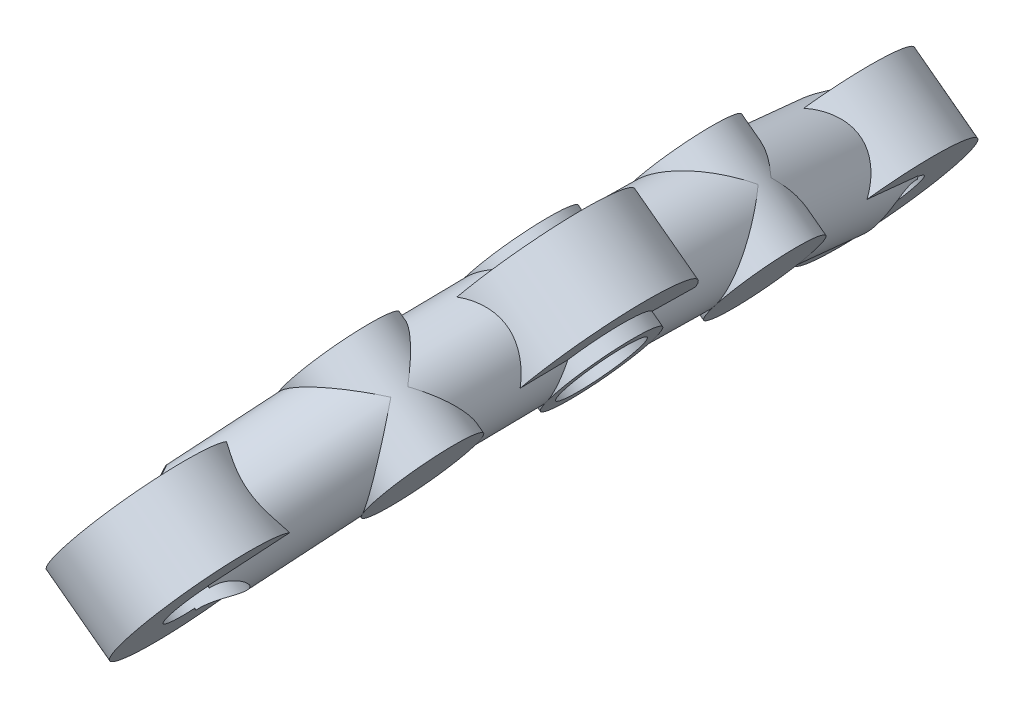
SolidWorks part; units mm, degrees
ref_plane "Alzado" through (0, 0, 0) normal (0, 0, 1) x (1, 0, 0)
ref_plane "Planta" through (0, 0, 0) normal (0, 1, 0) x (1, 0, 0)
ref_plane "Vista lateral" through (0, 0, 0) normal (1, 0, 0) x (0, 0, -1)
sketch3d "Sk_Arco_1"
  line L0 (-231.3637, 348.9396, -26) -> (-228.3681, 352.9429, -13)
  dimension "D1" = 13.9284
sweep "Arco_1" add path "Sk_Arco_1" circular profile diameter 8 parameters "D3"=8
sketch3d "Sk_Arco_2"
  line L0 (-228.3681, 352.9429, -13) -> (-227.769, 353.7435, 0)
  dimension "D1" = 13.0384
sweep "Arco_2" add path "Sk_Arco_2" circular profile diameter 8 parameters "D3"=8
sketch3d "Sk_Arco_3"
  line L0 (-227.769, 353.7435, 0) -> (-228.3681, 352.9429, 13)
  dimension "D1" = 13.0384
sweep "Arco_3" add path "Sk_Arco_3" circular profile diameter 8 parameters "D3"=8
sketch3d "Sk_Arco_4"
  line L0 (-228.3681, 352.9429, 13) -> (-231.3637, 348.9396, 26)
  dimension "D1" = 13.9284
sweep "Arco_4" add path "Sk_Arco_4" circular profile diameter 8 parameters "D3"=8
sketch3d "Sk_Arco_codo_1"
  line L0 (-225.1655, 350.5463, -13) -> (-231.5707, 355.3394, -13)
  dimension "D1" = 8
sweep "Arco_codo_1" add path "Sk_Arco_codo_1" circular profile diameter 8 parameters "D3"=8
sketch3d "Sk_Arco_codo_2"
  line L0 (-224.5664, 351.347, 0) -> (-230.9716, 356.14, 0)
  dimension "D1" = 8
sweep "Arco_codo_2" add path "Sk_Arco_codo_2" circular profile diameter 8 parameters "D3"=8
sketch3d "Sk_Arco_codo_3"
  line L0 (-225.1655, 350.5463, 13) -> (-231.5707, 355.3394, 13)
  dimension "D1" = 8
sweep "Arco_codo_3" add path "Sk_Arco_codo_3" circular profile diameter 8 parameters "D3"=8
sketch3d "Sk_Boss_izq"
  line L0 (-228.9618, 347.1422, -26) -> (-233.7657, 350.737, -26)
  dimension "D1" = 6
sweep "Boss_izq" add path "Sk_Boss_izq" circular profile diameter 12 parameters "D3"=12
sketch3d "Sk_Boss_dcho"
  line L0 (-228.9618, 347.1422, 26) -> (-233.7657, 350.737, 26)
  dimension "D1" = 6
sweep "Boss_dcho" add path "Sk_Boss_dcho" circular profile diameter 12 parameters "D3"=12
sketch3d "Sk_Boss_centro"
  line L0 (-225.367, 351.9461, 0) -> (-230.1709, 355.5409, 0)
  dimension "D1" = 6
sweep "Boss_centro" add path "Sk_Boss_centro" circular profile diameter 14 parameters "D3"=14
sketch3d "Sk_Pivote_izq"
  line L0 (-228.1611, 346.5431, -26) -> (-234.5664, 351.3361, -26)
  dimension "D1" = 8
sweep "Pivote_izq" cut path "Sk_Pivote_izq" circular profile diameter 5 parameters "D3"=5
sketch3d "Sk_Pivote_dcho"
  line L0 (-228.1611, 346.5431, 26) -> (-234.5664, 351.3361, 26)
  dimension "D1" = 8
sweep "Pivote_dcho" cut path "Sk_Pivote_dcho" circular profile diameter 5 parameters "D3"=5
sketch3d "Sk_Taladro_tornillo"
  line L0 (-224.5664, 351.347, 0) -> (-230.9716, 356.14, 0)
  dimension "D1" = 8
sweep "Taladro_tornillo" cut path "Sk_Taladro_tornillo" circular profile diameter 6 parameters "D3"=6
